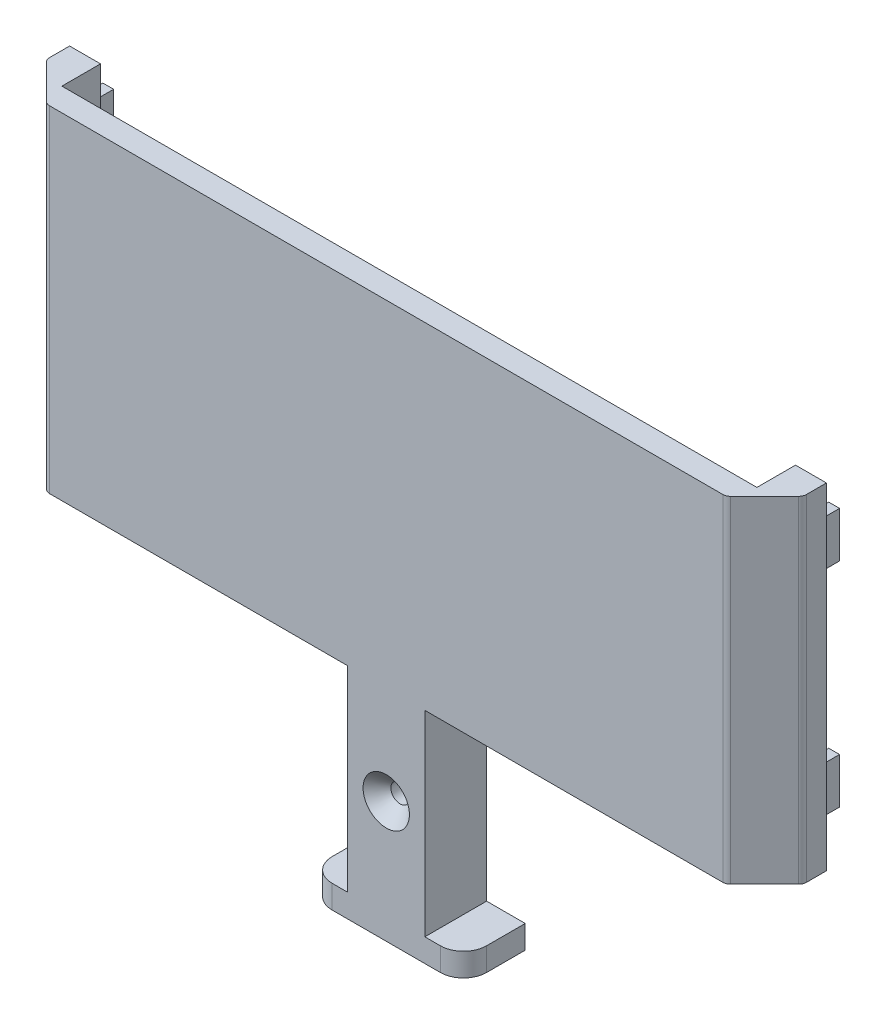
SolidWorks part; units mm, degrees
ref_plane "Front Plane" through (0, 0, 0) normal (0, 0, 1) x (1, 0, 0)
ref_plane "Top Plane" through (0, 0, 0) normal (0, 1, 0) x (1, 0, 0)
ref_plane "Right Plane" through (0, 0, 0) normal (1, 0, 0) x (0, 0, -1)
sketch "Sketch2" plane through (0, 0, 0) normal (0, 0, 1) x (1, 0, 0)
  line L1 (48, 19.25) -> (-48, 19.25)
  line L2 (48, 19.25) -> (48, -19.25)
  line L3 (48, -19.25) -> (-48, -19.25)
  line L4 (-48, 19.25) -> (-48, -19.25)
  line L5 (48, 19.25) -> (-48, -19.25) construction
  line L6 (48, -19.25) -> (-48, 19.25) construction
  point P0 (0, 0)
  dimension "D1" = 96
  dimension "D2" = 38.5
extrude "Boss-Extrude1" add sketch "Sketch2" along normal blind 3
sketch "Sketch3" plane through (0, 0, 0) normal (1, 0, 0) x (0, 0, -1)
  line L0 (0, 13.75) -> (0, 15.25)
  line L1 (0, -19.25) -> (0, 19.25) construction
  line L2 (0, 15.25) -> (1.75, 15.25)
  line L3 (1.75, 13.75) -> (0, 13.75)
  line L4 (0, 0) -> (15.587, 0) construction
  line L5 (0, -15.25) -> (1.75, -15.25)
  line L6 (0, -13.75) -> (0, -15.25)
  line L7 (1.75, -13.75) -> (0, -13.75)
  arc A0 (1.75, 15.25) -> (1.75, 13.75) centre (1.75, 14.5) cw
  arc A1 (1.75, -15.25) -> (1.75, -13.75) centre (1.75, -14.5) ccw
  dimension "D1" = 14.5
  dimension "D2" = 1.5
  dimension "D3" = 1.75
extrude "Boss-Extrude2" add sketch "Sketch3" along normal blind 45 and the other way blind 20 contours L5 A1 L7 L6 region at (0, -14.5, -1.1755)
extrude "Boss-Extrude3" add sketch "Sketch3<3>" along normal blind 20 and the other way blind 45 contours L3 L0 L2 A0
sketch "Sketch3<3>" plane through (0, 0, 0) normal (1, 0, 0) x (0, 0, -1) same geometry as "Sketch3"
sketch "Sketch4" plane through (0, 0, 0) normal (0, 0, -1) x (-1, 0, 0)
  circle A0 centre (0, 0) radius 1.375
  dimension "D1" = 2.75
extrude "Cut-Extrude1" cut sketch "Sketch4" against normal through all draft 45
sketch "Sketch5" plane through (-48, 0, 0) normal (-1, 0, 0) x (0, 0, 1)
  line L0 (0, 19.25) -> (0, -19.25) construction
  line L1 (3, -19.25) -> (-5, -19.25)
  line L2 (3, -19.25) -> (3, -24.25)
  line L3 (3, -24.25) -> (-5, -24.25)
  line L4 (-5, -19.25) -> (-5, -24.25)
  dimension "D1" = 5
  dimension "D2" = 5
extrude "Boss-Extrude4" add sketch "Sketch5" against normal through all
sketch "Sketch6" plane through (0, -19.25, 0) normal (0, 1, 0) x (1, 0, 0)
  line L0 (48, 0) -> (-48, 0) construction
  line L1 (-48, 5) -> (-45, 5)
  line L2 (-48, 5) -> (-48, 0)
  line L3 (-48, 0) -> (-45, 0)
  line L4 (-45, 5) -> (-45, 0)
  line L5 (0, 0) -> (0, 12.346) construction
  line L6 (48, 0) -> (45, 0)
  line L7 (45, 5) -> (45, 0)
  line L8 (48, 5) -> (45, 5)
  line L9 (48, 5) -> (48, 0)
  point P8 (-45, 2.5)
  dimension "D1" = 3
extrude "Boss-Extrude5" add sketch "Sketch6" along normal through all
sketch "Sketch7" plane through (0, 0, 0) normal (0, 0, -1) x (-1, 0, 0)
  circle A0 centre (0, 0) radius 7.5
  circle A1 centre (0, 0) radius 3.5
  dimension "D1" = 15
  dimension "D2" = 7
extrude "Cut-Extrude2" cut sketch "Sketch7" against normal blind 2
other "Move Face1" face at (-48, -2.5, -1) offset 1 parameters "D1"=1
other "Move Face2" face at (48, -2.5, -1) offset 1 parameters "D1"=1
sketch "Sketch8" plane through (0, 0, -5) normal (0, 0, -1) x (-1, 0, 0)
  line L0 (-47, 19.25) -> (-47, -24.25) construction
  line L1 (-47.7, 14.25) -> (-46.3, 14.25)
  line L2 (-47.7, 14.25) -> (-47.7, 8.35)
  line L3 (-47.7, 8.35) -> (-46.3, 8.35)
  line L4 (-46.3, 14.25) -> (-46.3, 8.35)
  line L5 (-47.7, -13.35) -> (-46.3, -13.35)
  line L6 (-47.7, -13.35) -> (-47.7, -19.25)
  line L7 (-47.7, -19.25) -> (-46.3, -19.25)
  line L8 (-46.3, -13.35) -> (-46.3, -19.25)
  line L9 (46.3, 14.25) -> (47.7, 14.25)
  line L10 (46.3, 14.25) -> (46.3, 8.35)
  line L11 (46.3, 8.35) -> (47.7, 8.35)
  line L12 (47.7, 14.25) -> (47.7, 8.35)
  line L13 (46.3, -13.35) -> (47.7, -13.35)
  line L14 (46.3, -13.35) -> (46.3, -19.25)
  line L15 (46.3, -19.25) -> (47.7, -19.25)
  line L16 (47.7, -13.35) -> (47.7, -19.25)
  line L17 (-49, 19.25) -> (-45, 19.25) construction
  line L18 (-49, -24.25) -> (49, -24.25) construction
  line L19 (47, 19.25) -> (47, -24.25) construction
  line L20 (45, 19.25) -> (49, 19.25) construction
  point P21 (-47, 14.25)
  point P29 (47, 14.25)
  dimension "D1" = 1.4
  dimension "D2" = 5.9
  dimension "D3" = 5
  dimension "D4" = 5
extrude "Boss-Extrude6" add sketch "Sketch8" along normal blind 3
sketch "Sketch9" plane through (0, -24.25, 0) normal (0, -1, 0) x (1, 0, 0)
  line L0 (49, 3) -> (-49, 3) construction
  line L1 (-5, -5) -> (5, -5)
  line L2 (-5, -5) -> (-5, 3)
  line L3 (-5, 3) -> (5, 3)
  line L4 (5, -5) -> (5, 3)
  line L5 (-5, -5) -> (5, 3) construction
  line L6 (-5, 3) -> (5, -5) construction
  line L7 (49, -5) -> (-49, -5) construction
  point P0 (0, 0)
  point P10 (0, -1)
  dimension "D1" = 10
extrude "Boss-Extrude7" add sketch "Sketch9" along normal blind 25.4
sketch "Sketch11" plane through (0, 0, 0) normal (1, 0, 0) x (0, 0, -1)
  line L1 (5, -49.65) -> (-3, -49.65)
  line L2 (5, -49.65) -> (5, -52.65)
  line L3 (5, -52.65) -> (-3, -52.65)
  line L4 (-3, -49.65) -> (-3, -52.65)
  line L5 (5, -49.65) -> (-3, -49.65) construction
  line L6 (5, -49.65) -> (5, -24.25) construction
  dimension "D1" = 3
extrude "Boss-Extrude8" add sketch "Sketch11" along normal mid plane 20
chamfer "Chamfer1" distance 5 angle 45 2 edges at (-49, -2.5, 3) (49, -2.5, 3)
fillet "Fillet1" radius 1 4 edges at (-49, -2.5, -2) (-44, -2.5, 3) (49, -2.5, -2) (44, -2.5, 3)
fillet "Fillet2" [suppressed] radius 1
fillet "Fillet3" radius 3 2 edges at (-10, -51.15, 3) (10, -51.15, 3)
other "Move Face3" flip direction yes face at (0, -19.25, -2.5) offset 2 parameters "D1"=2
hole_wizard "CSK for M2 Flat Head Machine Screw1" positions "Sketch12" profile "Sketch13" countersink size "M2" standard "ANSI Metric" end condition through all
sketch "Sketch12" plane through (0, 0, 3) normal (0, 0, 1) x (1, 0, 0)
  line L0 (0, -36.95) -> (5, -36.95) construction
  line L1 (5, -49.65) -> (5, -24.25) construction
  point P0 (0, -36.95)
sketch "Sketch13" plane through (0, -36.95, 3) normal (1, 0, 0) x (0, -1, 0)
  line L0 (0, 0) -> (0, 11)
  line L1 (0, 11) -> (1.2, 11)
  line L2 (1.2, 11) -> (1.2, 1.8)
  line L3 (1.2, 1.8) -> (3, 0)
  line L5 (3, 0) -> (0, 0)
  line L6 (-1.2, 1.8) -> (-3, 0) construction
  line L11 (0, -6.35) -> (0, 107.95) construction
  dimension "Thru Hole Dia." = 2.4
  dimension "Thru Hole Depth" = 11
  dimension "Near C'Sink Dia." = 6
  dimension "Near C'Sink Angle" = 90
